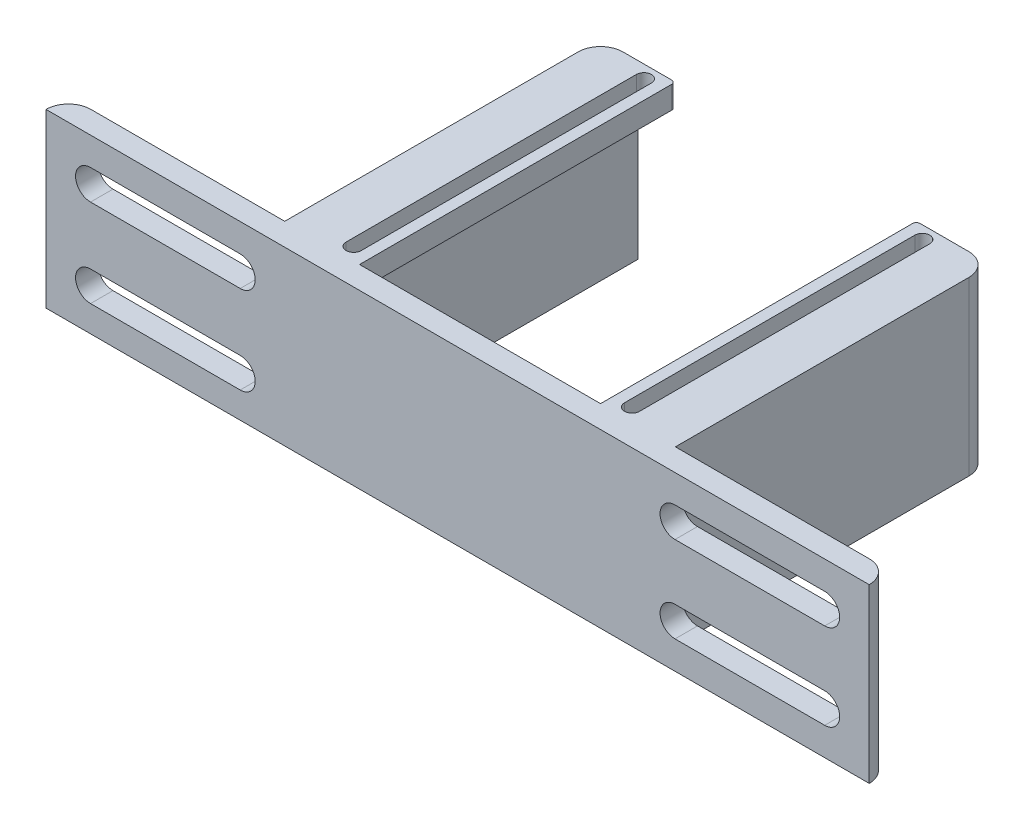
SolidWorks part; units mm, degrees
ref_plane "Front Plane" through (0, 0, 0) normal (0, 0, 1) x (1, 0, 0)
ref_plane "Top Plane" through (0, 0, 0) normal (0, 1, 0) x (1, 0, 0)
ref_plane "Right Plane" through (0, 0, 0) normal (1, 0, 0) x (0, 0, -1)
sketch "Sketch1" plane through (0, 0, 0) normal (0, 1, 0) x (1, 0, 0)
  line L0 (-55, 0) -> (55, 0)
  line L1 (55, 0) -> (55, 3)
  line L2 (55, 3) -> (26.1, 3)
  line L3 (26.1, 3) -> (26.1, 45.2)
  line L4 (26.1, 45.2) -> (21.1, 45.2)
  line L5 (21.1, 45.2) -> (21.1, 3)
  line L6 (21.1, 3) -> (-21.1, 3)
  line L7 (0, 0) -> (0, 100) construction
  line L9 (-55, 0) -> (-55, 3)
  line L10 (21.1, 3) -> (16.1, 3)
  line L11 (21.1, 3) -> (21.1, 45.2)
  line L12 (21.1, 45.2) -> (16.1, 45.2)
  line L13 (16.1, 3) -> (16.1, 45.2)
  line L14 (-55, 3) -> (-26.1, 3)
  line L15 (-26.1, 3) -> (-26.1, 45.2)
  line L16 (-26.1, 45.2) -> (-21.1, 45.2)
  line L17 (-21.1, 45.2) -> (-16.1, 45.2)
  line L18 (-21.1, 45.2) -> (-21.1, 3)
  line L19 (-16.1, 3) -> (-16.1, 45.2)
  point P20 (0, 3)
  dimension "D1" = 28.9
  dimension "D2" = 3
  dimension "D3" = 5
  dimension "D4" = 21.1
  dimension "D5" = 3
  dimension "D6" = 42.2
  dimension "D7" = 5
extrude "Boss-Extrude5" add sketch "Sketch1" along normal blind 23 contours L18 L6 L5 L4 L3 L2 L1 L0 L9 L14 L15 L16
sketch "Sketch3" plane through (0, 0, -3) normal (0, 0, -1) x (-1, 0, 0)
  line L1 (-21.1, 23) -> (-16.1, 23)
  line L2 (-21.1, 23) -> (-21.1, 20)
  line L3 (-21.1, 20) -> (-16.1, 20)
  line L4 (-16.1, 23) -> (-16.1, 20)
  line L5 (21.1, 23) -> (16.1, 23)
  line L6 (21.1, 23) -> (21.1, 20)
  line L7 (21.1, 20) -> (16.1, 20)
  line L8 (16.1, 23) -> (16.1, 20)
  dimension "D1" = 3
  dimension "D2" = 5
  dimension "D3" = 3
  dimension "D4" = 5
extrude "Boss-Extrude7" add sketch "Sketch3" along normal blind 42.2
sketch "Sketch4" plane through (0, 23, 0) normal (0, 1, 0) x (1, 0, 0)
  line L0 (16.1, 45.2) -> (26.1, 45.2) construction
sketch "Sketch5" plane through (0, 20, 0) normal (0, -1, 0) x (-1, 0, 0)
  line L0 (18.6, 45.2) -> (18.6, 3) construction
  line L1 (16.1, 45.2) -> (21.1, 45.2) construction
  line L2 (16.1, 3) -> (21.1, 3) construction
  line L3 (21.1, 24.1) -> (16.1, 24.1) construction
  line L4 (21.1, 45.2) -> (21.1, 3) construction
  line L5 (16.1, 45.2) -> (16.1, 3) construction
  line L6 (-18.6, 3) -> (-18.6, 45.2) construction
  line L7 (-21.1, 3) -> (-16.1, 3) construction
  line L8 (-16.1, 45.2) -> (-26.1, 45.2) construction
  line L9 (-18.6, 45.2) -> (-21.1, 24.1) construction
  line L10 (-21.1, 45.2) -> (-21.1, 3) construction
  line L11 (-18.6, 43.4907) -> (-18.6, 4.7093) construction
  line L12 (-17.6, 43.4907) -> (-17.6, 4.7093)
  line L13 (-19.6, 43.4907) -> (-19.6, 4.7093)
  line L14 (-18.6, 24.1) -> (18.6, 24.1) construction
  line L15 (-18.6, 3.7093) -> (19.35, 3.7093) construction
  line L16 (18.6, 4.7093) -> (18.6, 43.4907) construction
  line L17 (17.6, 4.7093) -> (17.6, 43.4907)
  line L18 (19.6, 4.7093) -> (19.6, 43.4907)
  arc A0 (-17.6, 43.4907) -> (-19.6, 43.4907) centre (-18.6, 43.4907) ccw
  arc A1 (-19.6, 4.7093) -> (-17.6, 4.7093) centre (-18.6, 4.7093) ccw
  arc A2 (17.6, 4.7093) -> (19.6, 4.7093) centre (18.6, 4.7093) ccw
  arc A3 (19.6, 43.4907) -> (17.6, 43.4907) centre (18.6, 43.4907) ccw
  point P23 (-18.6, 24.1)
  point P34 (18.6, 24.1)
  point P39 (0, 0)
  point P40 (18.6, 24.1)
extrude "Cut-Extrude3" cut sketch "Sketch5" against normal blind 42.2 contours L12 A1 L13 A0
extrude "Cut-Extrude4" cut sketch "Sketch5<4>" against normal blind 42.2 contours L18 A3 L17 A2
sketch "Sketch5<4>" plane through (0, 20, 0) normal (0, -1, 0) x (-1, 0, 0) same geometry as "Sketch5"
fillet "Fillet1" radius 3 1 edges at (-26.1, 11.5, -45.2)
fillet "Fillet2" radius 3 1 edges at (26.1, 11.5, -45.2)
fillet "Fillet3" radius 0.5 1 edges at (-16.1, 21.5, -45.2)
fillet "Fillet4" radius 0.5 1 edges at (16.1, 21.5, -45.2)
fillet "Fillet5" radius 3 1 edges at (55, 11.5, -3)
fillet "Fillet6" radius 3 1 edges at (-55, 11.5, -3)
sketch "Sketch6" plane through (0, 0, -3) normal (0, 0, -1) x (-1, 0, 0)
  line L0 (-52, 11.5) -> (-26.1, 11.5) construction
  line L1 (-52, 23) -> (-52, 0) construction
  line L2 (-26.1, 23) -> (-26.1, 0) construction
  line L3 (-26.1, 11.5) -> (-39.05, 11.5) construction
  line L4 (-39.05, 11.5) -> (-39.05, 23) construction
  line L5 (-52, 23) -> (-26.1, 23) construction
  line L6 (-39.05, 11.5) -> (-39.05, 0) construction
  line L7 (-52, 0) -> (-26.1, 0) construction
  line L8 (-39.05, 5.75) -> (-52, 5.75) construction
  line L9 (-52, 5.75) -> (-39.05, 5.75) construction
  line L10 (-39.05, 5.75) -> (-26.1, 5.75) construction
  line L11 (-39.05, 17.25) -> (-52, 17.25) construction
  line L12 (-52, 17.25) -> (-39.05, 17.25) construction
  line L13 (-39.05, 17.25) -> (-26.1, 17.25) construction
  line L14 (-29.05, 17.25) -> (-49.05, 17.25) construction
  line L15 (-29.05, 15.25) -> (-49.05, 15.25)
  line L16 (-29.05, 19.25) -> (-49.05, 19.25)
  line L17 (-29.05, 5.75) -> (-49.05, 5.75) construction
  line L18 (-29.05, 3.75) -> (-49.05, 3.75)
  line L19 (-29.05, 7.75) -> (-49.05, 7.75)
  arc A0 (-29.05, 15.25) -> (-29.05, 19.25) centre (-29.05, 17.25) ccw
  arc A1 (-49.05, 19.25) -> (-49.05, 15.25) centre (-49.05, 17.25) ccw
  arc A2 (-29.05, 3.75) -> (-29.05, 7.75) centre (-29.05, 5.75) ccw
  arc A3 (-49.05, 7.75) -> (-49.05, 3.75) centre (-49.05, 5.75) ccw
  point P21 (-39.05, 17.25)
  point P27 (-39.05, 5.75)
extrude "Cut-Extrude5" cut sketch "Sketch6" against normal blind 42.2
sketch "Sketch7" plane through (0, 0, -3) normal (0, 0, -1) x (-1, 0, 0)
  line L0 (26.1, 11.5) -> (52, 11.5) construction
  line L1 (26.1, 23) -> (26.1, 0) construction
  line L2 (52, 0) -> (52, 23) construction
  line L3 (52, 11.5) -> (52, 23) construction
  line L4 (39.05, 11.5) -> (39.05, 23) construction
  line L5 (52, 23) -> (26.1, 23) construction
  line L6 (39.05, 23) -> (39.05, 0) construction
  line L7 (52, 0) -> (26.1, 0) construction
  line L8 (26.1, 23) -> (26.1, 0) construction
  line L9 (52, 17.25) -> (26.1, 17.25) construction
  line L10 (39.05, 0) -> (39.05, 11.5) construction
  line L11 (39.05, 0) -> (39.05, 11.5) construction
  line L12 (26.1, 0) -> (26.1, 11.5) construction
  line L13 (26.1, 5.503) -> (52, 5.503) construction
  line L14 (29.05, 5.503) -> (49.05, 5.503) construction
  line L15 (29.05, 7.503) -> (49.05, 7.503)
  line L16 (29.05, 3.503) -> (49.05, 3.503)
  line L17 (49.05, 17.25) -> (29.05, 17.25) construction
  line L18 (49.05, 15.25) -> (29.05, 15.25)
  line L19 (49.05, 19.25) -> (29.05, 19.25)
  arc A0 (29.05, 7.503) -> (29.05, 3.503) centre (29.05, 5.503) ccw
  arc A1 (49.05, 3.503) -> (49.05, 7.503) centre (49.05, 5.503) ccw
  arc A2 (49.05, 15.25) -> (49.05, 19.25) centre (49.05, 17.25) ccw
  arc A3 (29.05, 19.25) -> (29.05, 15.25) centre (29.05, 17.25) ccw
  point P25 (39.05, 5.503)
  point P31 (39.05, 17.25)
extrude "Cut-Extrude6" cut sketch "Sketch7" against normal blind 42.2 contours L19 A3 L18 A2
extrude "Cut-Extrude7" cut sketch "Sketch7<3>" against normal blind 42.2 contours L15 A1 L16 A0
sketch "Sketch7<3>" plane through (0, 0, -3) normal (0, 0, -1) x (-1, 0, 0) same geometry as "Sketch7"
